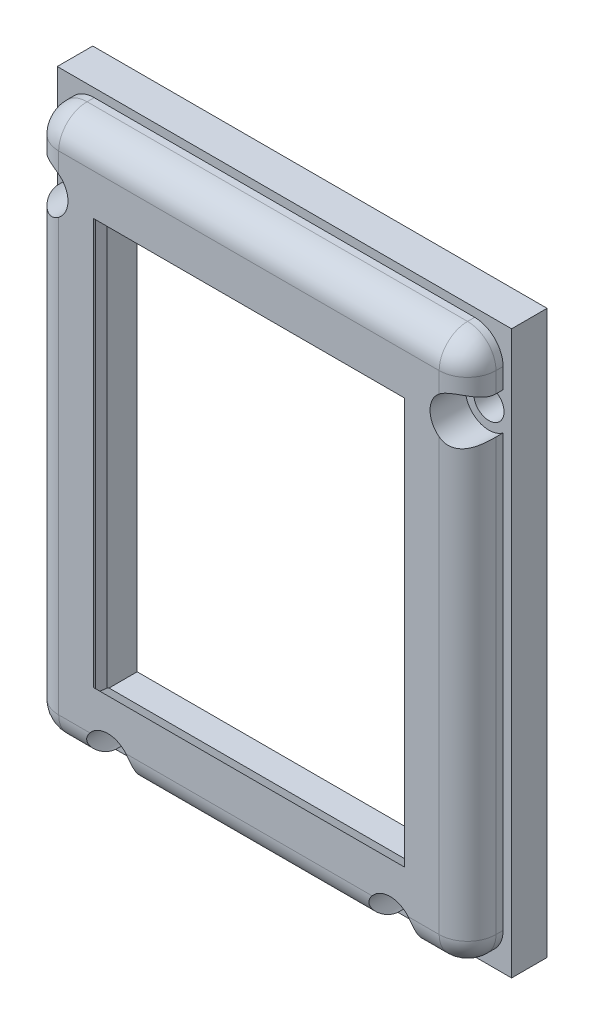
SolidWorks part; units mm, degrees
ref_plane "Front Plane" through (0, 0, 0) normal (0, 0, 1) x (1, 0, 0)
ref_plane "Top Plane" through (0, 0, 0) normal (0, 1, 0) x (1, 0, 0)
ref_plane "Right Plane" through (0, 0, 0) normal (1, 0, 0) x (0, 0, -1)
sketch "Model" plane through (0, 0, 0) normal (0, 0, 1) x (1, 0, 0)
  line L0 (0, 0) -> (114.2864, 0) construction
  line L1 (114.2864, 0) -> (114.2864, 50.7864) construction
  line L2 (114.2864, 50.7864) -> (0, 50.7864) construction
  line L3 (0, 50.7864) -> (0, 0) construction
  line L4 (13.1379, 4.5435) -> (23.2721, 4.5435) construction
  line L5 (23.2721, 4.5435) -> (23.2721, 42.2805) construction
  line L6 (23.2721, 42.2805) -> (13.1379, 42.2805) construction
  line L7 (13.1379, 42.2805) -> (13.1379, 4.5435) construction
  line L8 (31.4005, 4.5225) -> (41.5347, 4.5225) construction
  line L9 (41.5347, 4.5225) -> (41.5347, 42.3015) construction
  line L10 (41.5347, 42.3015) -> (31.4005, 42.3015) construction
  line L11 (31.4005, 42.3015) -> (31.4005, 4.5225) construction
  line L12 (46.2086, 7.3498) -> (78.8994, 7.3498)
  line L13 (78.8994, 7.3498) -> (78.8994, 50.0406)
  line L14 (78.8994, 50.0406) -> (46.2086, 50.0406)
  line L15 (46.2086, 50.0406) -> (46.2086, 7.3498)
  line L16 (3.8168, 33.0268) -> (8.8696, 33.0268) construction
  line L17 (8.8696, 33.0268) -> (8.8696, 43.1596) construction
  line L18 (8.8696, 43.1596) -> (3.8168, 43.1596) construction
  line L19 (3.8168, 43.1596) -> (3.8168, 33.0268) construction
  line L20 (2.5466, 21.3426) -> (10.1398, 21.3426) construction
  line L21 (10.1398, 21.3426) -> (10.1398, 29.4438) construction
  line L22 (10.1398, 29.4438) -> (2.5466, 29.4438) construction
  line L23 (2.5466, 29.4438) -> (2.5466, 21.3426) construction
  line L24 (2.5466, 8.6426) -> (10.1398, 8.6426) construction
  line L25 (10.1398, 8.6426) -> (10.1398, 16.7438) construction
  line L26 (10.1398, 16.7438) -> (2.5466, 16.7438) construction
  line L27 (2.5466, 16.7438) -> (2.5466, 8.6426) construction
  line L28 (62.554, 50.0406) -> (62.554, 7.3498) construction
  line L29 (46.2086, 28.6952) -> (78.8994, 28.6952) construction
  line L31 (42.234, 3.5492) -> (82.874, 3.5492)
  line L32 (90.991, 1.5367) -> (106.9676, 1.5367) construction
  line L33 (106.9676, 1.5367) -> (106.9676, 4.6101) construction
  line L34 (106.9676, 4.6101) -> (90.991, 4.6101) construction
  line L35 (90.991, 4.6101) -> (90.991, 1.5367) construction
  line L36 (42.234, 3.5492) -> (42.234, 53.8412)
  line L37 (42.234, 53.8412) -> (82.874, 53.8412)
  line L38 (82.874, 3.5492) -> (82.874, 53.8412)
  line L39 (42.234, 3.5492) -> (82.874, 53.8412) construction
  line L40 (42.234, 53.8412) -> (82.874, 3.5492) construction
  circle A0 centre (111.125, 47.625) radius 1.5 construction
  circle A1 centre (3.175, 47.625) radius 1.5 construction
  circle A2 centre (3.175, 3.175) radius 1.5 construction
  circle A3 centre (111.125, 3.175) radius 1.5 construction
  circle A4 centre (44.2722, 47.0662) radius 1.35
  circle A5 centre (49.9364, 5.5118) radius 1.35
  circle A6 centre (75.184, 5.5118) radius 1.35
  circle A7 centre (80.8482, 47.0662) radius 1.35
  circle A8 centre (97.79, 25.4) radius 9.3853 construction
  circle A9 centre (97.8662, 33.9598) radius 2.7686 construction
  circle A10 centre (16.764, 47.879) radius 2.7813 construction
  circle A11 centre (26.162, 47.879) radius 2.7813 construction
  circle A12 centre (35.56, 47.879) radius 2.7813 construction
  point P60 (62.554, 28.6952)
  point P63 (62.554, 28.6952)
extrude "Boss-Extrude1" add sketch "Model" along normal blind 3.175 contours L14 L15 L12 L13 | L37 L38 L31 L36 | A4 | A5 | A6 | A7 region at (62.554, 28.6952, 0)
sketch "Sketch1" plane through (0, 0, 3.175) normal (0, 0, 1) x (1, 0, 0)
  line L0 (62.554, 53.8412) -> (62.554, 3.5492) construction
  line L1 (42.234, 53.8412) -> (82.874, 53.8412) construction
  line L2 (42.234, 3.5492) -> (82.874, 3.5492) construction
  line L3 (42.234, 28.6952) -> (82.874, 28.6952) construction
  line L4 (42.234, 3.5492) -> (42.234, 53.8412) construction
  line L5 (82.874, 3.5492) -> (82.874, 53.8412) construction
  line L7 (46.2086, 7.3498) -> (78.8994, 7.3498)
  line L8 (46.2086, 7.3498) -> (46.2086, 50.0406)
  line L9 (46.2086, 50.0406) -> (78.8994, 50.0406)
  line L10 (78.8994, 7.3498) -> (78.8994, 50.0406)
  line L11 (46.2086, 7.3498) -> (78.8994, 50.0406) construction
  line L12 (46.2086, 50.0406) -> (78.8994, 7.3498) construction
  line L13 (48.6399, 10.5248) -> (76.4681, 10.5248)
  line L14 (48.6399, 10.5248) -> (48.6399, 46.8656)
  line L15 (48.6399, 46.8656) -> (76.4681, 46.8656)
  line L16 (76.4681, 10.5248) -> (76.4681, 46.8656)
  line L17 (48.6399, 10.5248) -> (76.4681, 46.8656) construction
  line L18 (48.6399, 46.8656) -> (76.4681, 10.5248) construction
  point P12 (62.554, 28.6952)
  point P13 (62.554, 28.6952)
  point P19 (62.554, 28.6952)
  dimension "D1" = 3.175
extrude "Boss-Extrude2" add sketch "Sketch1" along normal blind 3.175 separate body
sketch "Sketch2" plane through (0, 0, 3.175) normal (0, 0, 1) x (1, 0, 0)
  line L0 (62.554, 3.5492) -> (62.554, 53.8412) construction
  line L1 (42.234, 3.5492) -> (82.874, 3.5492) construction
  line L2 (42.234, 53.8412) -> (82.874, 53.8412) construction
  line L3 (82.874, 28.6952) -> (42.234, 28.6952) construction
  line L4 (82.874, 3.5492) -> (82.874, 53.8412) construction
  line L5 (42.234, 3.5492) -> (42.234, 53.8412) construction
  line L7 (82.112, 4.3112) -> (42.996, 4.3112)
  line L8 (82.112, 4.3112) -> (82.112, 53.0792)
  line L9 (82.112, 53.0792) -> (42.996, 53.0792)
  line L10 (42.996, 4.3112) -> (42.996, 53.0792)
  line L11 (82.112, 4.3112) -> (42.996, 53.0792) construction
  line L12 (82.112, 53.0792) -> (42.996, 4.3112) construction
  line L13 (78.8994, 7.3498) -> (46.2086, 7.3498)
  line L14 (78.8994, 7.3498) -> (78.8994, 50.0406)
  line L15 (78.8994, 50.0406) -> (46.2086, 50.0406)
  line L16 (46.2086, 7.3498) -> (46.2086, 50.0406)
  line L17 (78.8994, 7.3498) -> (46.2086, 50.0406) construction
  line L18 (78.8994, 50.0406) -> (46.2086, 7.3498) construction
  line L19 (78.8994, 50.0406) -> (46.2086, 50.0406) construction
  line L20 (46.2086, 50.0406) -> (46.2086, 7.3498) construction
  point P12 (62.554, 28.6952)
  point P13 (62.554, 28.6952)
  point P18 (62.554, 28.6952)
  dimension "D1" = 0.762
  dimension "D2" = 0.762
extrude "Boss-Extrude4" add sketch "Sketch2" along normal blind 3.175
fillet "Fillet1" radius 2.54 2 edges at (62.554, 4.3112, 6.35) (62.554, 53.0792, 6.35)
fillet "Fillet2" radius 2.54 10 edges at (42.996, 53.0792, 3.4925) (42.996, 52.3352, 5.6061) (42.996, 4.3112, 3.4925) (42.996, 5.0551, 5.6061) (82.112, 4.3112, 3.4925) (82.112, 5.0551, 5.6061) (82.112, 53.0792, 3.4925) (82.112, 52.3352, 5.6061) (42.996, 28.6952, 6.35) (82.112, 28.6952, 6.35)
chamfer "Chamfer9" distance 3.175 angle 42 2 edges at (48.6399, 28.6952, 3.175) (76.4681, 28.6952, 3.175) first distance on face at (48.6399, 28.6952, 4.7625) first distance on face at (76.4681, 28.6952, 4.7625)
chamfer "Chamfer10" distance 3.175 angle 45 2 edges at (62.554, 46.8656, 3.175) (62.554, 10.5248, 3.175)
sketch "Sketch4" plane through (0, 0, 0) normal (0, 0, -1) x (-1, 0, 0)
  circle A0 centre (-80.8482, 47.0662) radius 1.35
  circle A1 centre (-44.2722, 47.0662) radius 1.35
  circle A2 centre (-49.9364, 5.5118) radius 1.35
  circle A3 centre (-75.184, 5.5118) radius 1.35
  circle A4 centre (-75.184, 5.5118) radius 1.35 construction
  circle A5 centre (-49.9364, 5.5118) radius 1.35 construction
  circle A6 centre (-80.8482, 47.0662) radius 1.35 construction
  circle A8 centre (-44.2722, 47.0662) radius 1.35 construction
extrude "Cut-Extrude1" cut sketch "Sketch4" against normal through all
chamfer "Chamfer11" distance 0.889 angle 19 2 edges at (62.554, 50.0406, 3.175) (62.554, 7.3498, 3.175) first distance on face at (62.554, 48.824, 4.3916) first distance on face at (62.554, 8.5664, 4.3916)
chamfer "Chamfer12" distance 1.143 angle 19 2 edges at (46.2086, 28.6952, 3.6498) (78.8994, 28.6952, 3.6498) first distance on face at (47.0652, 28.6952, 4.6011) first distance on face at (78.0428, 28.6952, 4.6011)
sketch "Sketch5" plane through (0, 0, 6.35) normal (0, 0, 1) x (1, 0, 0)
  circle A0 centre (44.2722, 47.0662) radius 2.0955
  circle A1 centre (80.8482, 47.0662) radius 2.0955
  circle A2 centre (75.184, 5.5118) radius 2.0955
  circle A3 centre (49.9364, 5.5118) radius 2.0955
  dimension "D1" = 4.191
extrude "Cut-Extrude2" cut sketch "Sketch5" against normal up to surface (3.175 mm away) contours A0 | A1 | A2 | A3 up to face at (62.554, 28.6952, 3.175)
